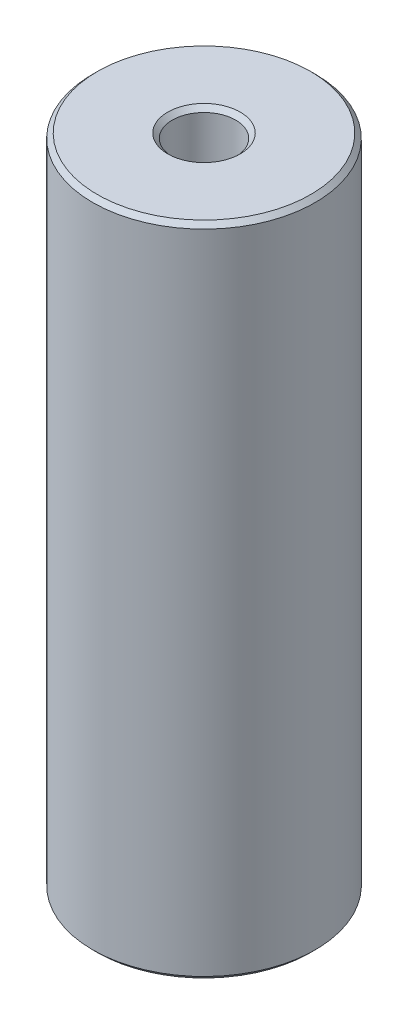
SolidWorks part; units mm, degrees
ref_plane "Front Plane" through (0, 0, 0) normal (0, 0, 1) x (1, 0, 0)
ref_plane "Top Plane" through (0, 0, 0) normal (0, 1, 0) x (1, 0, 0)
ref_plane "Right Plane" through (0, 0, 0) normal (1, 0, 0) x (0, 0, -1)
sketch "Sketch1" plane through (0, 0, 0) normal (0, 1, 0) x (1, 0, 0)
  circle A0 centre (0, 0) radius 5
  dimension "SLEEVE_OD" = 10
extrude "Boss-Extrude1" add sketch "Sketch1" along normal blind 29.5032
sketch "Sketch2" plane through (0, 0, 0) normal (0, 1, 0) x (1, 0, 0)
  circle A0 centre (0, 0) radius 1.4234
  dimension "BORE_D" = 2.8467
extrude "Cut-Extrude1" cut sketch "Sketch2" along normal through all
chamfer "Chamfer1" distance 0.2066 angle 45 4 edges at (0, 29.5032, 1.4234) (0, 0, 1.4234) (0, 0, 5) (0, 29.5032, 5)
